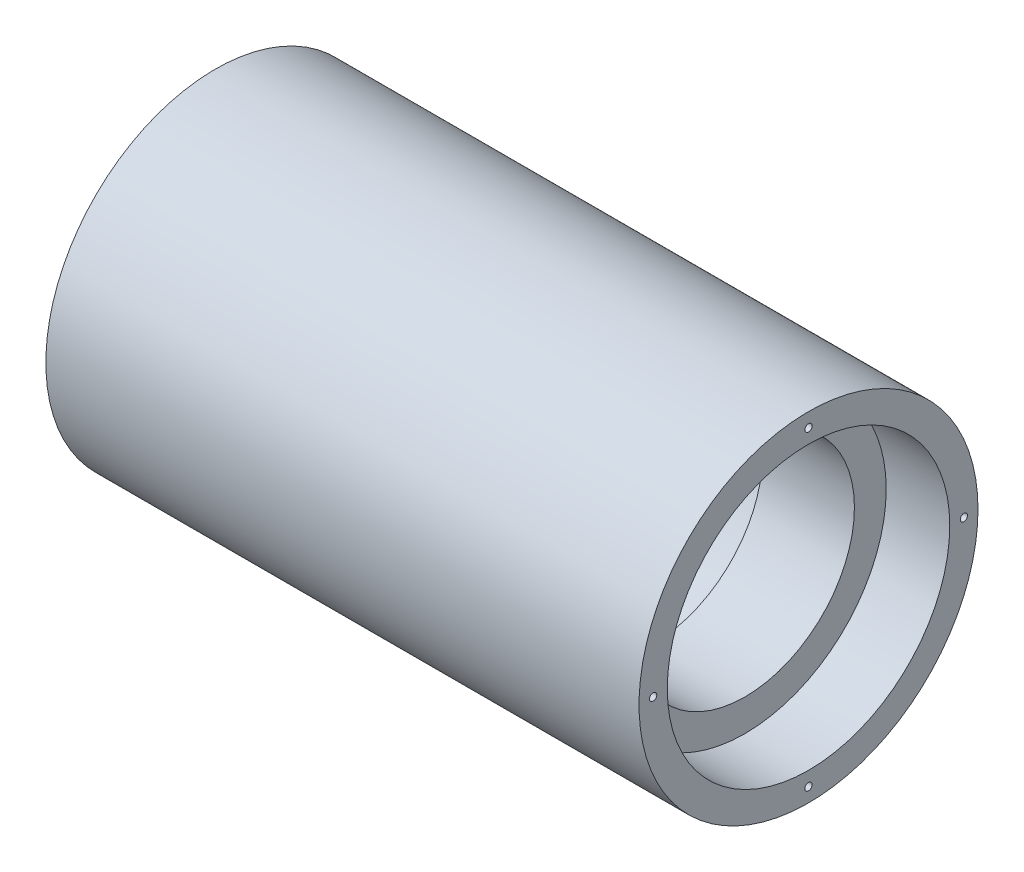
SolidWorks part; units mm, degrees
material "Cast Alloy Steel"
ref_plane "Front" through (0, 0, 0) normal (0, 0, 1) x (1, 0, 0)
ref_plane "Top" through (0, 0, 0) normal (0, 1, 0) x (1, 0, 0)
ref_plane "Right" through (0, 0, 0) normal (1, 0, 0) x (0, 0, -1)
sketch "Sketch2" plane through (0, 0, 0) normal (1, 0, 0) x (0, -1, 0)
  circle A0 centre (0, 0) radius 48
  dimension "D1" = 96
extrude "Boss-Extrude1" add sketch "Sketch2" along normal blind 84 and the other way blind 84
sketch "Sketch3" plane through (0, 0, 0) normal (1, 0, 0) x (0, -1, 0)
  circle A0 centre (0, 0) radius 40
  dimension "D1" = 80
extrude "Cut-Extrude1" cut sketch "Sketch3" against normal blind 50 and the other way blind 40
sketch "Sketch4" plane through (0, 0, 0) normal (1, 0, 0) x (0, -1, 0)
  circle A0 centre (0, 0) radius 31
  dimension "D1" = 62
extrude "Cut-Extrude2" cut sketch "Sketch4" against normal through all both and the other way through all
fillet "Fillet1" radius 5 2 edges at (40, 0, -40) (-50, 0, -40)
sketch "Sketch5" plane through (0, 0, 0) normal (-1, 0, 0) x (0, 0, -1)
  circle A0 centre (0, 0) radius 40
  dimension "D1" = 80
extrude "Cut-Extrude3" cut sketch "Sketch5" against normal up to next from offset 66 offset against normal yes
sketch "Sketch6" plane through (-84, 0, 0) normal (-1, 0, 0) x (0, 0, 1)
  circle A0 centre (0, 0) radius 34
  dimension "D1" = 68
extrude "Cut-Extrude4" cut sketch "Sketch6" against normal blind 18.4
hole_wizard "M2.5x0.45 Tapped Hole1" positions "Sketch9" profile "Sketch11" tap size "M2.5x0.45" standard "ANSI Metric"
sketch "Sketch9" plane through (84, 0, 0) normal (1, 0, 0) x (0, 0, -1)
  circle A0 centre (0, 0) radius 40 construction
  point P30 (256.3539, 80.1032)
  point P32 (0, -44)
  point P34 (-44, 0)
  point P36 (0, 44)
  point P38 (44, 0)
  dimension "D1" = 88
  dimension "D2" = 44
  dimension "D3" = 44
  dimension "D4" = 88
  dimension "D5" = 256.3539
  dimension "D6" = 80.1032
sketch "Sketch11" plane through (84, 80.1032, -256.3539) normal (0, 1, 0) x (0, 0, -1)
  line L0 (0, 0) -> (0, 8.6159)
  line L1 (0, 8.6159) -> (1.025, 8)
  line L2 (1.025, 8) -> (1.025, 0)
  line L5 (1.025, 0) -> (0, 0)
  line L10 (0, 8.6159) -> (-1.025, 8) construction
  line L11 (0, -6.35) -> (0, 107.95) construction
  dimension "Tap Drill Dia." = 2.05
  dimension "Tap Drill Depth" = 8
  dimension "Drill Angle" = 118
cosmetic thread "Hole Thread2" parameters "D1"=5, "D2"=2.5
cosmetic thread "Hole Thread5" parameters "D1"=5, "D2"=2.5
cosmetic thread "Hole Thread6" parameters "D1"=5, "D2"=2.5
cosmetic thread "Hole Thread7" parameters "D1"=5, "D2"=2.5
hole_wizard "M2.5x0.45 Tapped Hole2" positions "Sketch12" profile "Sketch13" tap size "M2.5x0.45" standard "ANSI Metric"
sketch "Sketch12" plane through (-84, 0, 0) normal (-1, 0, 0) x (0, 0, 1)
  line L1 (-61.6, 0) -> (61.6, 0) construction
  line L2 (0, -61.6) -> (0, 61.6) construction
  point P0 (0, 41)
  point P4 (0, -41)
  point P6 (41, 0)
  point P9 (-41, 0)
  dimension "D1" = 82
  dimension "D2" = 82
  dimension "D3" = 41
  dimension "D4" = 41
sketch "Sketch13" plane through (-84, 41, 0) normal (0, 1, 0) x (0, 0, 1)
  line L0 (0, 0) -> (0, 8.6159)
  line L1 (0, 8.6159) -> (1.025, 8)
  line L2 (1.025, 8) -> (1.025, 0)
  line L5 (1.025, 0) -> (0, 0)
  line L10 (0, 8.6159) -> (-1.025, 8) construction
  line L11 (0, -6.35) -> (0, 107.95) construction
  dimension "Tap Drill Dia." = 2.05
  dimension "Tap Drill Depth" = 8
  dimension "Drill Angle" = 118
cosmetic thread "Hole Thread8" parameters "D1"=5, "D2"=2.5
cosmetic thread "Hole Thread9" parameters "D1"=5, "D2"=2.5
cosmetic thread "Hole Thread10" parameters "D1"=5, "D2"=2.5
cosmetic thread "Hole Thread12" parameters "D1"=5, "D2"=2.5
sketch "Sketch14" plane through (84, 0, 0) normal (1, 0, 0) x (0, 0, -1)
  circle A0 centre (0, 0) radius 34.825
  dimension "D1" = 69.65
